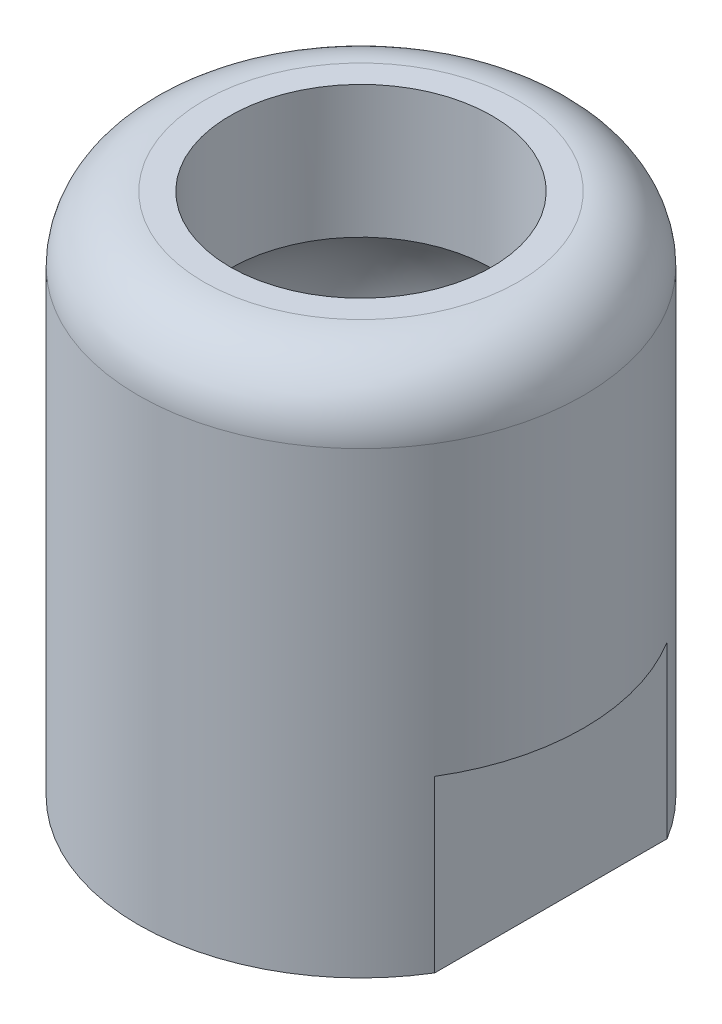
SolidWorks part; units mm, degrees
ref_plane "Front Plane" through (0, 0, 0) normal (0, 0, 1) x (1, 0, 0)
ref_plane "Top Plane" through (0, 0, 0) normal (0, 1, 0) x (1, 0, 0)
ref_plane "Right Plane" through (0, 0, 0) normal (1, 0, 0) x (0, 0, -1)
sketch "Sketch1" plane through (0, 0, 0) normal (0, 1, 0) x (1, 0, 0)
  circle A0 centre (0, 0) radius 11
  dimension "D1" = 22
extrude "Boss-Extrude1" add sketch "Sketch1" along normal blind 280
sketch "Sketch2" plane through (0, 280, 0) normal (0, 1, 0) x (1, 0, 0)
  circle A0 centre (0, 0) radius 17
  dimension "D1" = 34
extrude "Boss-Extrude2" add sketch "Sketch2" along normal blind 40
sketch "Sketch3" plane through (0, 0, 0) normal (0, -1, 0) x (1, 0, 0)
  circle A0 centre (0, 0) radius 17 construction
  circle A1 centre (0, 0) radius 17
extrude "Boss-Extrude3" add sketch "Sketch3" along normal blind 40
fillet "Fillet1" radius 5 1 edges at (0, -40, -17)
fillet "Fillet2" radius 5 1 edges at (0, 320, 17)
sketch "Sketch4" plane through (0, 0, 0) normal (0, 0, 1) x (1, 0, 0)
  line L1 (17, 280) -> (14.5, 280)
  line L2 (17, 280) -> (17, 293)
  line L3 (17, 293) -> (14.5, 293)
  line L4 (14.5, 280) -> (14.5, 293)
  line L5 (-17, 280) -> (-14.5, 280)
  line L6 (-17, 280) -> (-17, 293)
  line L7 (-17, 293) -> (-14.5, 293)
  line L8 (-14.5, 280) -> (-14.5, 293)
  line L10 (17, 0) -> (14.5, 0)
  line L11 (17, 0) -> (17, -13)
  line L12 (14.5, 0) -> (14.5, -13)
  line L13 (17, -13) -> (14.5, -13)
  line L14 (-17, 0) -> (-14.5, 0)
  line L15 (-17, -13) -> (-14.5, -13)
  line L16 (-17, 0) -> (-17, -13)
  line L17 (-14.5, 0) -> (-14.5, -13)
  dimension "D1" = 13
  dimension "D2" = 29
extrude "Cut-Extrude1" cut sketch "Sketch4" against normal blind 40 and the other way blind 40
sketch "Sketch5" plane through (0, -40, 0) normal (0, -1, 0) x (1, 0, 0)
  circle A0 centre (0, 0) radius 10
  dimension "D1" = 20
extrude "Cut-Extrude2" cut sketch "Sketch5" against normal blind 35
sketch "Sketch6" plane through (0, 320, 0) normal (0, 1, 0) x (1, 0, 0)
  circle A0 centre (0, 0) radius 10
  dimension "D1" = 20
extrude "Cut-Extrude3" cut sketch "Sketch6" against normal blind 35
sketch "Sketch7" plane through (0, 0, 0) normal (0, 0, 1) x (1, 0, 0)
  line L0 (0, 314.8974) -> (0, 289.8974)
  line L1 (0, -9.7955) -> (0, -34.7955)
  arc A0 (0, 289.8974) -> (0, 314.8974) centre (0, 302.3974) ccw
  arc A1 (0, -34.7955) -> (0, -9.7955) centre (0, -22.2955) ccw
  dimension "D1" = 25
  dimension "D2" = 25
revolve "Cut-Revolve4" cut sketch "Sketch7" angle 360 about axis through (0, 285, 0) along (0, 1, 0)
sketch "Sketch8" plane through (0, 0, 0) normal (0, 0, 1) x (1, 0, 0)
  line L1 (-51.8921, 280) -> (51.836, 280)
  line L2 (-51.8921, 280) -> (-51.8921, -41.25)
  line L3 (-51.8921, -41.25) -> (51.836, -41.25)
  line L4 (51.836, 280) -> (51.836, -41.25)
  line L5 (-14.5, 280) -> (14.5, 280) construction
extrude "Cut-Extrude4" cut sketch "Sketch8" against normal mid plane 50
sketch "Sketch9" plane through (0, 280, 0) normal (0, -1, 0) x (1, 0, 0)
  circle A0 centre (0, 0) radius 6.5
  dimension "D1" = 13
extrude "Cut-Extrude5" cut sketch "Sketch9" against normal blind 20
thread "Thread1" pitch 1.5 method cut profile "Thread Profile1" start angle 0, offset 0, length 26, pitch 1.5, diameter 13
ref_plane "Plane1" through (6.5, 280, 0) normal (0, 0, 1) x (1, 0, 0)
sketch "Thread Profile1" plane through (6.5, 280, 0) normal (0, 0, 1) x (1, 0, 0)
  line L0 (0, 0) -> (0, 1.5) construction
  line L1 (0, 0) -> (0.8119, 0.4687)
  line L2 (0.8119, 0.4687) -> (0.8119, 0.6562)
  line L3 (0.8119, 0.6562) -> (0, 1.125)
  line L4 (0.8119, 0.5625) -> (0, 0.5625) construction
  line L11 (0, 0) -> (0, 1.125)
  point P2 (0, 0)
  dimension "Pitch" = 1.5
  dimension "Profile_Angle" = 60
  dimension "Profile_Land" = 0.1875
  dimension "Profile_Height" = 0.8119
